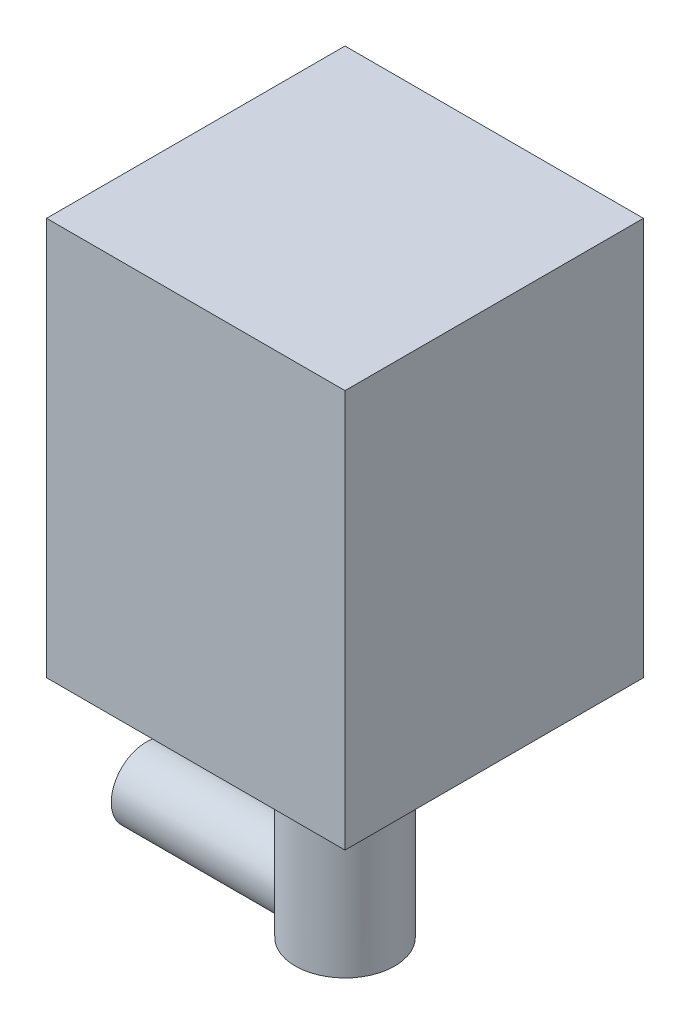
SolidWorks part; units mm, degrees
ref_plane "Front Plane" through (0, 0, 0) normal (1, 0, 0) x (0, 1, 0)
ref_plane "Top Plane" through (0, 0, 0) normal (0, 0, 1) x (0, 1, 0)
ref_plane "Right Plane" through (0, 0, 0) normal (0, 1, 0) x (-1, 0, 0)
sketch "Sketch1" plane through (0, 0, 0) normal (0, 0, 1) x (0, 1, 0)
  line L1 (0, 0) -> (-20, 0)
  line L2 (0, 0) -> (0, 15)
  line L3 (0, 15) -> (-20, 15)
  line L4 (-20, 0) -> (-20, 15)
  dimension "D1" = 20
  dimension "D2" = 15
extrude "Boss-Extrude1" add sketch "Sketch1" along normal blind 15
sketch "Sketch2" plane through (0, -20, 0) normal (0, -1, 0) x (1, 0, 0)
  line L1 (-15, 15) -> (-15, 0) construction
  line L2 (-15, 0) -> (0, 0) construction
  circle A0 centre (-7.5, 7.5) radius 2.5
  dimension "D1" = 5
  dimension "D2" = 7.5
  dimension "D3" = 7.5
extrude "Boss-Extrude2" add sketch "Sketch2" along normal blind 11.3
sketch "Sketch3" plane through (0, 0, 0) normal (1, 0, 0) x (0, 1, 0)
  line L0 (-31.3, 10) -> (-31.3, 5) construction
  line L1 (-31.3, 5) -> (-20, 5) construction
  circle A0 centre (-29.55, 7.5) radius 1.75
  circle A1 centre (-24.55, 7.5) radius 1.75
  dimension "D1" = 3.5
  dimension "D2" = 5
  dimension "D3" = 2.5
extrude "Boss-Extrude3" add sketch "Sketch3" against normal blind 10 from offset 7.5 offset against normal yes
